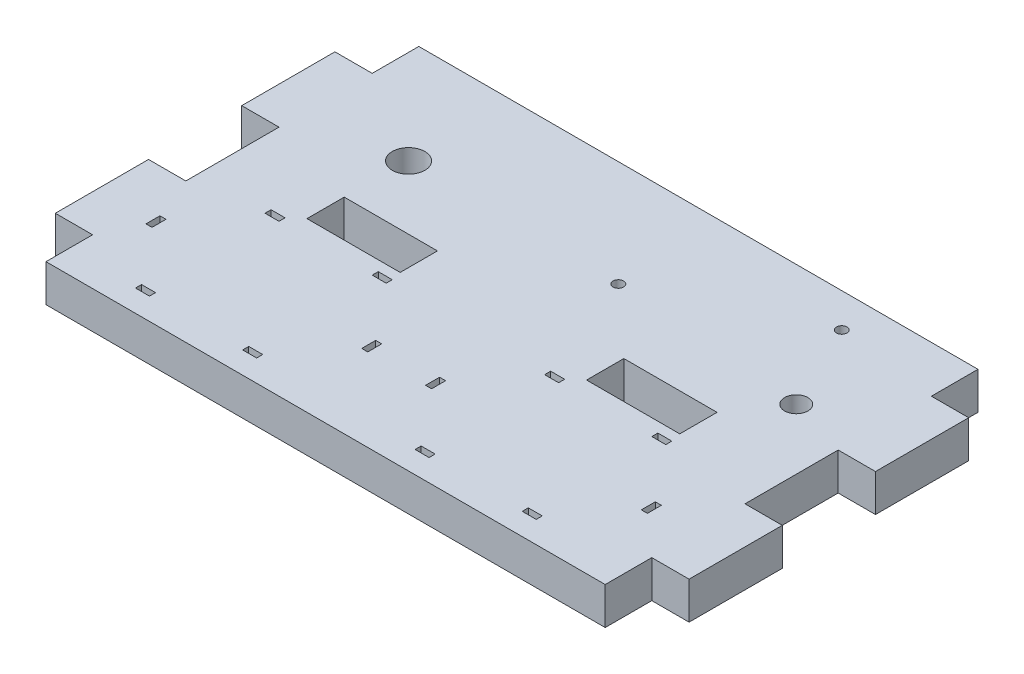
SolidWorks part; units mm, degrees
ref_plane "Front Plane" through (0, 0, 0) normal (0, 0, 1) x (1, 0, 0)
ref_plane "Top Plane" through (0, 0, 0) normal (0, 1, 0) x (1, 0, 0)
ref_plane "Right Plane" through (0, 0, 0) normal (1, 0, 0) x (0, 0, -1)
sketch "Sketch1" plane through (0, 0, 0) normal (0, 1, 0) x (1, 0, 0)
  line L0 (-66.0627, 0) -> (65.2437, 0) construction
  line L1 (-60, 40) -> (60, 40)
  line L2 (-60, 40) -> (-60, -40)
  line L3 (-60, -40) -> (60, -40)
  line L4 (60, 40) -> (60, -40)
  line L5 (27.5, -7.5) -> (27.5, -34) construction
  line L6 (5, -7.5) -> (50, -7.5) construction
  line L7 (5, -7.5) -> (5, -34) construction
  line L8 (5, -34) -> (50, -34) construction
  line L9 (50, -7.5) -> (50, -34) construction
  line L10 (-5.21, 35.09) -> (40, 35.09) construction
  line L11 (-5.21, 35.09) -> (-5.21, 15) construction
  line L12 (-5.21, 15) -> (40, 15) construction
  line L13 (40, 35.09) -> (40, 15) construction
  line L14 (-5.21, 35.09) -> (40, 15) construction
  line L15 (-5.21, 15) -> (40, 35.09) construction
  line L16 (5, -20.75) -> (50, -20.75) construction
  line L17 (14.5, -35.3) -> (17.5, -35.3)
  line L18 (14.5, -7.5) -> (17.5, -7.5)
  line L19 (14.5, -7.5) -> (14.5, -6.2)
  line L20 (14.5, -6.2) -> (17.5, -6.2)
  line L21 (17.5, -7.5) -> (17.5, -6.2)
  line L22 (17.5, -34) -> (17.5, -35.3)
  line L23 (14.5, -34) -> (17.5, -34)
  line L24 (14.5, -34) -> (14.5, -35.3)
  line L25 (40.5, -7.5) -> (40.5, -6.2)
  line L26 (40.5, -6.2) -> (37.5, -6.2)
  line L27 (40.5, -7.5) -> (37.5, -7.5)
  line L28 (37.5, -7.5) -> (37.5, -6.2)
  line L29 (40.5, -34) -> (40.5, -35.3)
  line L30 (37.5, -34) -> (37.5, -35.3)
  line L31 (40.5, -34) -> (37.5, -34)
  line L32 (40.5, -35.3) -> (37.5, -35.3)
  line L33 (51.3, -22.25) -> (50, -22.25)
  line L34 (3.7, -19.25) -> (5, -19.25)
  line L35 (3.7, -19.25) -> (3.7, -22.25)
  line L36 (3.7, -22.25) -> (5, -22.25)
  line L37 (5, -19.25) -> (5, -22.25)
  line L38 (51.3, -19.25) -> (50, -19.25)
  line L39 (51.3, -19.25) -> (51.3, -22.25)
  line L40 (50, -19.25) -> (50, -22.25)
  line L41 (-2.5, -62.4684) -> (-2.5, 56.3378) construction
  line L42 (-43.323, 17.6273) -> (-60, 17.6273) construction
  line L44 (-40, 4) -> (-24.658, 4) construction
  line L45 (-39.823, 21.1273) -> (-39.823, 4) construction
  line L46 (40, 4) -> (68, 4) construction
  line L48 (-55, -19.25) -> (-55, -22.25)
  line L49 (-56.3, -19.25) -> (-56.3, -22.25)
  line L50 (-56.3, -19.25) -> (-55, -19.25)
  line L51 (-10, -19.25) -> (-10, -22.25)
  line L52 (-8.7, -22.25) -> (-10, -22.25)
  line L53 (-8.7, -19.25) -> (-8.7, -22.25)
  line L54 (-8.7, -19.25) -> (-10, -19.25)
  line L55 (-56.3, -22.25) -> (-55, -22.25)
  line L56 (-45.5, -35.3) -> (-42.5, -35.3)
  line L57 (-45.5, -34) -> (-42.5, -34)
  line L58 (-42.5, -34) -> (-42.5, -35.3)
  line L59 (-45.5, -34) -> (-45.5, -35.3)
  line L60 (-42.5, -7.5) -> (-42.5, -6.2)
  line L61 (-45.5, -7.5) -> (-42.5, -7.5)
  line L62 (-45.5, -6.2) -> (-42.5, -6.2)
  line L63 (-45.5, -7.5) -> (-45.5, -6.2)
  line L64 (-19.5, -34) -> (-19.5, -35.3)
  line L65 (-19.5, -34) -> (-22.5, -34)
  line L66 (-22.5, -34) -> (-22.5, -35.3)
  line L67 (-22.5, -7.5) -> (-22.5, -6.2)
  line L68 (-19.5, -6.2) -> (-22.5, -6.2)
  line L69 (-19.5, -7.5) -> (-19.5, -6.2)
  line L70 (-19.5, -7.5) -> (-22.5, -7.5)
  line L71 (-19.5, -35.3) -> (-22.5, -35.3)
  circle A0 centre (-39.823, 17.6273) radius 3.5
  circle A1 centre (47, 14) radius 2.5
  circle A2 centre (38.07, 32.68) radius 1.13
  circle A3 centre (5.56, 17.26) radius 1.13
  point P4 (60, 0)
  point P6 (0, 40)
  point P23 (17.395, 25.045)
  point P46 (5, -20.75)
  dimension "D5" = 10
  dimension "D10" = 15
  dimension "D17" = 2.26
  dimension "D18" = 2.26
  dimension "D11" = 7
  dimension "D12" = 5
  dimension "D23" = 13
  dimension "D24" = 10
  dimension "D1" = 120
  dimension "D2" = 80
  dimension "D3" = 26.5
  dimension "D4" = 45
  dimension "D6" = 7.5
  dimension "D7" = 20
  dimension "D8" = 1.3
  dimension "D9" = 3
  dimension "D13" = 45.21
  dimension "D14" = 20.09
  dimension "D15" = 15
  dimension "D16" = 20
  dimension "D19" = 15.42
  dimension "D20" = 17.68
  dimension "D21" = 32.51
  dimension "D22" = 1.93
extrude "Boss-Extrude1" add sketch "Sketch1" along normal blind 8
sketch "Sketch2" plane through (0, 0, 0) normal (0, -1, 0) x (1, 0, 0)
  line L1 (7.8694, -17.26) -> (6.7147, -15.26)
  line L2 (6.7147, -15.26) -> (4.4053, -15.26)
  line L3 (4.4053, -15.26) -> (3.2506, -17.26)
  line L4 (3.2506, -17.26) -> (4.4053, -19.26)
  line L5 (4.4053, -19.26) -> (6.7147, -19.26)
  line L6 (6.7147, -19.26) -> (7.8694, -17.26)
  line L7 (40.3794, -32.68) -> (39.2247, -30.68)
  line L8 (39.2247, -30.68) -> (36.9153, -30.68)
  line L9 (36.9153, -30.68) -> (35.7606, -32.68)
  line L10 (35.7606, -32.68) -> (36.9153, -34.68)
  line L11 (36.9153, -34.68) -> (39.2247, -34.68)
  line L12 (39.2247, -34.68) -> (40.3794, -32.68)
  circle A0 centre (5.56, -17.26) radius 2 construction
  circle A1 centre (5.56, -17.26) radius 1.13 construction
  circle A2 centre (38.07, -32.68) radius 2 construction
  circle A3 centre (38.07, -32.68) radius 1.13 construction
  dimension "D1" = 4
  dimension "D2" = 4
extrude "Cut-Extrude1" cut sketch "Sketch2" against normal blind 4
sketch "Sketch3" plane through (0, 0, 0) normal (0, -1, 0) x (1, 0, 0)
  line L0 (-71.3423, 0) -> (66.6402, 0) construction
  line L1 (-40, 4) -> (-20, 4)
  line L2 (-40, 4) -> (-40, -4)
  line L3 (-40, -4) -> (-20, -4)
  line L4 (-20, 4) -> (-20, -4)
  point P7 (-20, 0)
  dimension "D1" = 8
  dimension "D2" = 20
  dimension "D3" = 20
extrude "Cut-Extrude2" cut sketch "Sketch3" against normal up to next
ref_plane "Plane1" through (0, 0, 0) normal (-1, 0, 0) x (0, 0, 1)
mirror "Mirror1" about plane through (0, 0, 0) normal (-1, 0, 0) of "Cut-Extrude2"
sketch "Sketch4" plane through (-60, 0, 0) normal (-1, 0, 0) x (0, 0, 1)
  line L0 (-40, 8) -> (40, 8) construction
  line L1 (30, 8) -> (10, 8)
  line L2 (30, 8) -> (30, 0)
  line L3 (30, 0) -> (10, 0)
  line L4 (10, 8) -> (10, 0)
  line L5 (-40, 0) -> (40, 0) construction
  line L6 (0, 18.5092) -> (0, -11.2621) construction
  line L7 (-10, 8) -> (-10, 0)
  line L8 (-30, 0) -> (-10, 0)
  line L9 (-30, 8) -> (-30, 0)
  line L10 (-30, 8) -> (-10, 8)
  dimension "D1" = 20
  dimension "D2" = 20
extrude "Boss-Extrude2" add sketch "Sketch4" along normal blind 8
mirror "Mirror2" about plane through (0, 0, 0) normal (-1, 0, 0) of "Boss-Extrude2"
